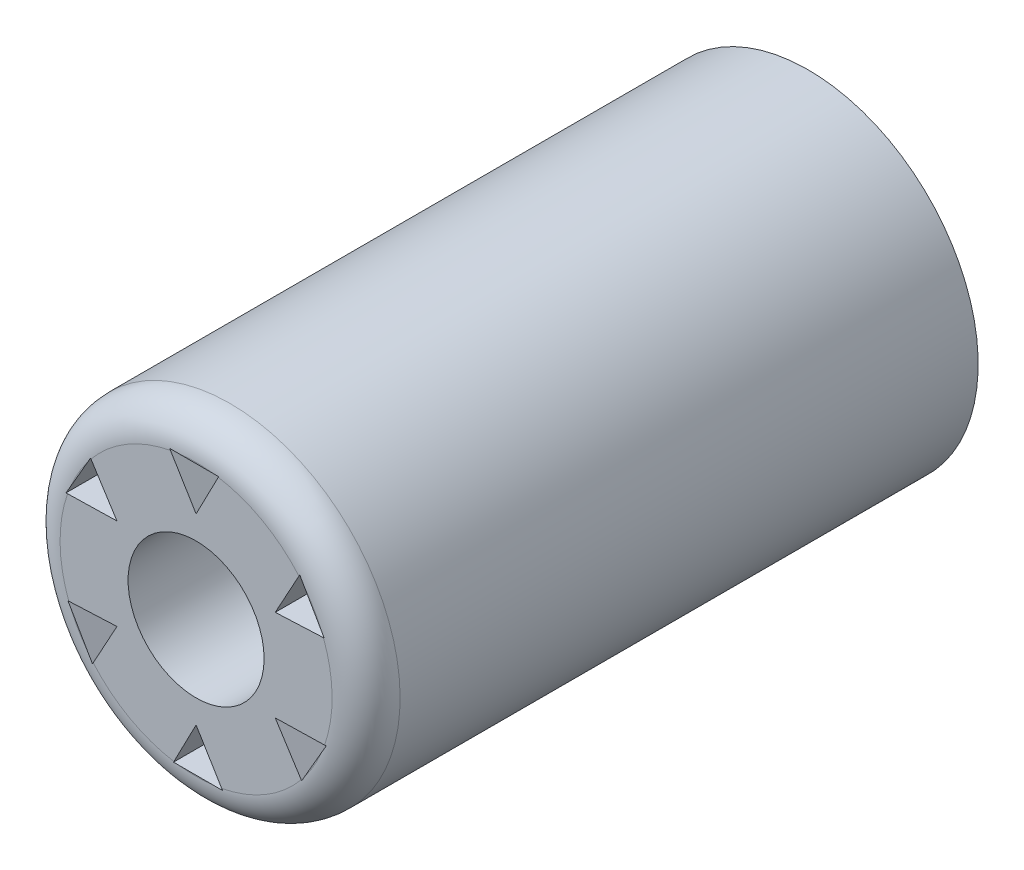
SolidWorks part; units mm, degrees
ref_plane "Front Plane" through (0, 0, 0) normal (0, 0, 1) x (1, 0, 0)
ref_plane "Top Plane" through (0, 0, 0) normal (0, 1, 0) x (1, 0, 0)
ref_plane "Right Plane" through (0, 0, 0) normal (1, 0, 0) x (0, 0, -1)
sketch "Sketch1" plane through (0, 0, 0) normal (0, 0, 1) x (1, 0, 0)
  circle A0 centre (0, 0) radius 50
  dimension "D1" = 100
extrude "Boss-Extrude1" add sketch "Sketch1" along normal blind 180
sketch "Sketch2" plane through (0, 0, 180) normal (0, 0, 1) x (1, 0, 0)
  line L0 (0, 26.8744) -> (-7.7814, 39.6782)
  line L1 (-7.7814, 39.6782) -> (6.6432, 39.6782)
  line L2 (6.6432, 39.6782) -> (0, 26.8744)
  line L3 (37.684, 14.0859) -> (23.2739, 13.4372)
  line L4 (23.2739, 13.4372) -> (30.4716, 26.578)
  line L5 (30.4716, 26.578) -> (37.684, 14.0859)
  line L6 (31.0407, -25.5923) -> (23.2739, -13.4372)
  line L7 (23.2739, -13.4372) -> (38.253, -13.1002)
  line L8 (38.253, -13.1002) -> (31.0407, -25.5923)
  line L9 (-6.6432, -39.6782) -> (0, -26.8744)
  line L10 (0, -26.8744) -> (7.7814, -39.6782)
  line L11 (7.7814, -39.6782) -> (-6.6432, -39.6782)
  line L12 (-37.684, -14.0859) -> (-23.2739, -13.4372)
  line L13 (-23.2739, -13.4372) -> (-30.4716, -26.578)
  line L14 (-30.4716, -26.578) -> (-37.684, -14.0859)
  line L15 (-31.0407, 25.5923) -> (-23.2739, 13.4372)
  line L16 (-23.2739, 13.4372) -> (-38.253, 13.1002)
  line L17 (-38.253, 13.1002) -> (-31.0407, 25.5923)
  point P21 (0, 0)
  dimension "D1" = 6
extrude "Cut-Extrude1" cut sketch "Sketch2" against normal blind 160
fillet "Fillet1" radius 10 1 edges at (50, 0, 180)
sketch "Sketch3" plane through (0, 0, 180) normal (0, 0, 1) x (1, 0, 0)
  circle A0 centre (0, 0) radius 20
  dimension "D1" = 40
extrude "Cut-Extrude2" cut sketch "Sketch3" against normal blind 180
